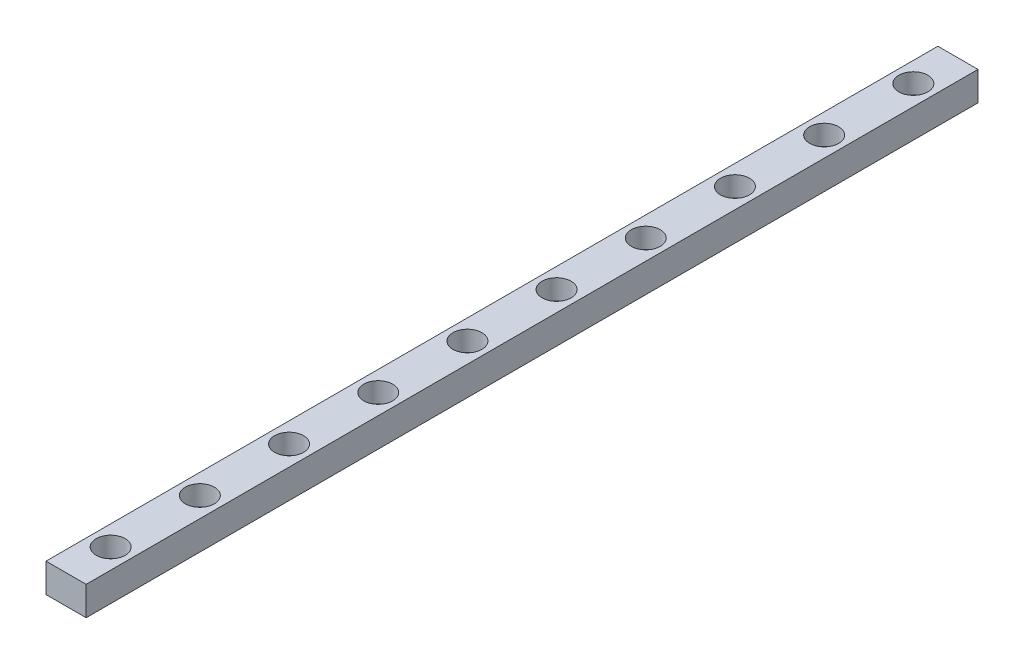
SolidWorks part; units mm, degrees
ref_plane "Front" through (0, 0, 0) normal (0, 0, 1) x (1, 0, 0)
ref_plane "Top" through (0, 0, 0) normal (0, 1, 0) x (1, 0, 0)
ref_plane "Right" through (0, 0, 0) normal (1, 0, 0) x (0, 0, -1)
sketch "Sketch1" plane through (0, 0, 0) normal (0, 0, 1) x (1, 0, 0)
  line L1 (0, 0) -> (9, 0)
  line L2 (0, 0) -> (0, 6.5)
  line L3 (0, 6.5) -> (9, 6.5)
  line L4 (9, 0) -> (9, 6.5)
  dimension "D1" = 9
  dimension "6.5" = 6.5
extrude "Boss-Extrude1" add sketch "Sketch1" along normal blind 200
hole_wizard "CBORE for M3 SHCS1" positions "Sketch2" profile "Sketch3" counterbore size "M3" standard "ANSI Metric" end condition through all
sketch "Sketch2" plane through (0, 6.5, 0) normal (0, 1, 0) x (1, 0, 0)
  line L0 (4.5, -190) -> (4.5, -200) construction
  line L1 (9, -200) -> (0, -200) construction
  line L2 (4.5, -10) -> (4.5, 0) construction
  line L3 (9, 0) -> (0, 0) construction
  point P0 (4.5, -190)
  point P36 (4.5, -170)
  point P37 (4.5, -150)
  point P38 (4.5, -130)
  point P39 (4.5, -110)
  point P40 (4.5, -90)
  point P41 (4.5, -70)
  point P42 (4.5, -50)
  point P60 (4.5, -30)
  point P61 (4.5, -10)
  dimension "D1" = 10
  dimension "D2" = 10
sketch "Sketch3" plane through (4.5, 6.5, 190) normal (1, 0, 0) x (0, 0, 1)
  line L0 (0, 0) -> (0, 6.5)
  line L1 (0, 6.5) -> (1.7, 6.5)
  line L3 (1.7, 6.5) -> (1.7, 4.5)
  line L4 (1.7, 4.5) -> (3.25, 4.5)
  line L5 (3.25, 4.5) -> (3.25, 0)
  line L7 (3.25, 0) -> (0, 0)
  line L11 (0, -6.35) -> (0, 107.95) construction
  dimension "Thru Hole Dia." = 3.4
  dimension "Thru Hole Depth" = 6.5
  dimension "C'Bore Dia." = 6.5
  dimension "C'Bore Depth" = 4.5
